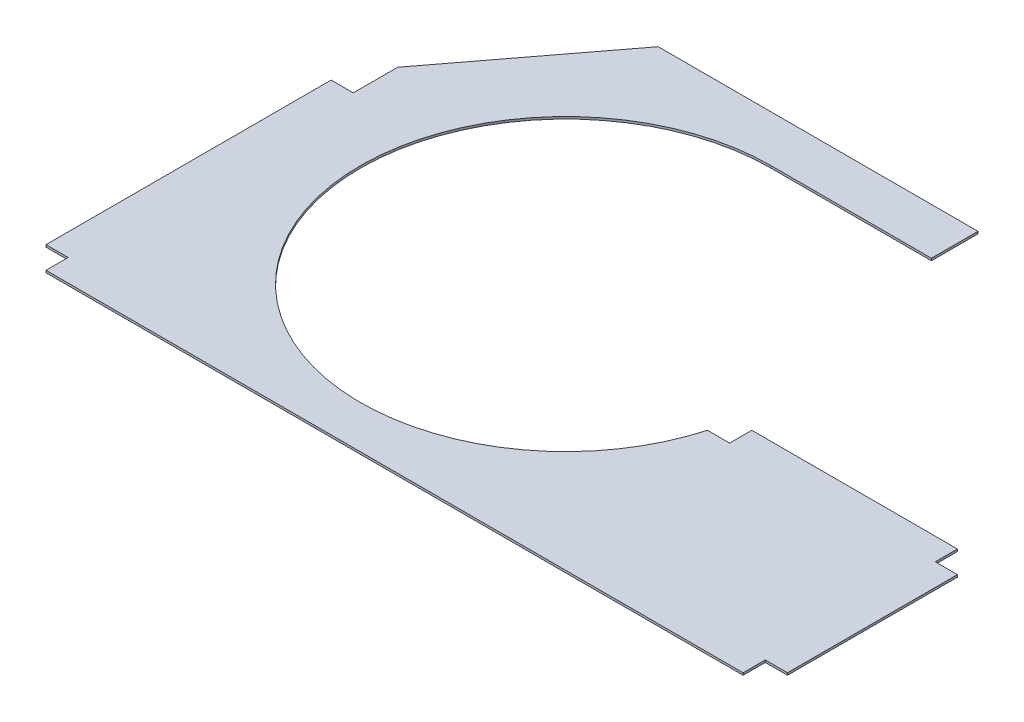
SolidWorks part; units mm, degrees
ref_plane "Front Plane" through (0, 0, 0) normal (0, 0, 1) x (1, 0, 0)
ref_plane "Top Plane" through (0, 0, 0) normal (0, 1, 0) x (1, 0, 0)
ref_plane "Right Plane" through (0, 0, 0) normal (1, 0, 0) x (0, 0, -1)
sketch "Sketch1" plane through (0, 0, 0) normal (0, 1, 0) x (1, 0, 0)
  line L0 (0, 0) -> (20, 0)
  line L1 (20, 0) -> (20, -20)
  line L2 (20, -20) -> (648.38, -20)
  line L3 (648.38, -20) -> (648.38, 0)
  line L4 (648.38, 0) -> (668.38, 0)
  line L5 (668.38, 0) -> (668.38, 153.21)
  line L7 (0, 0) -> (0, 257)
  line L9 (121.3895, 430.4594) -> (409.6583, 430.4594)
  line L10 (265, 388.4594) -> (409.6583, 388.4594)
  line L11 (409.6583, 430.4594) -> (409.6583, 388.4594)
  line L12 (0, 257) -> (20, 257)
  line L13 (20, 257) -> (20, 297)
  line L14 (20, 297) -> (121.3895, 430.4594)
  line L15 (668.38, 153.21) -> (648.38, 153.21)
  line L16 (648.38, 153.21) -> (648.38, 173.21)
  line L18 (648.38, 173.21) -> (463.0449, 173.21)
  line L19 (463.0449, 173.21) -> (463.0449, 153.21)
  line L20 (463.0449, 153.21) -> (443.0449, 153.21)
  arc A0 (443.0449, 153.21) -> (265, 388.4594) centre (265, 203.4594) cw
  point P13 (20, 277)
  point P21 (197.7394, 208.4594)
  dimension "D13" = 185
  dimension "D1" = 628.38
  dimension "D2" = 20
  dimension "D3" = 20
  dimension "D4" = 20
  dimension "D5" = 257
  dimension "D6" = 20
  dimension "D7" = 40
  dimension "D8" = 450.4594
  dimension "D9" = 153.21
  dimension "D10" = 20
  dimension "D11" = 20
  dimension "D12" = 42
  dimension "D14" = 265
  dimension "D15" = 20
  dimension "D16" = 20
extrude "Boss-Extrude1" add sketch "Sketch1" along normal blind 2
